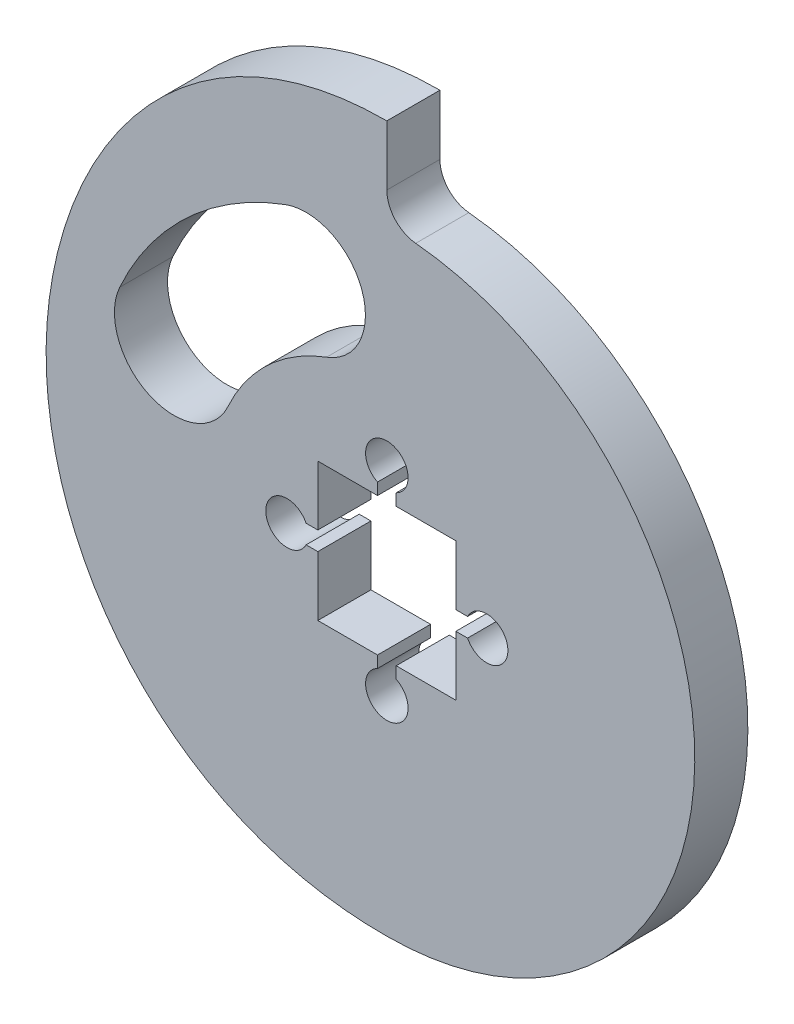
SolidWorks part; units mm, degrees
material "AISI 1020 Steel, Cold Rolled"
ref_plane "Front Plane" through (0, 0, 0) normal (0, 0, 1) x (1, 0, 0)
ref_plane "Top Plane" through (0, 0, 0) normal (0, 1, 0) x (1, 0, 0)
ref_plane "Right Plane" through (0, 0, 0) normal (1, 0, 0) x (0, 0, -1)
other "Center of Mass"
sketch "Sketch1" plane through (0, 0, 0) normal (0, 0, 1) x (1, 0, 0)
  line L0 (1.1176, -8.255) -> (8.255, -8.255)
  line L1 (-8.255, 8.255) -> (-1.1176, 8.255)
  line L2 (-8.255, 8.255) -> (-8.255, 1.1176)
  line L3 (-8.255, -8.255) -> (-1.1176, -8.255)
  line L4 (8.255, 8.255) -> (8.255, 1.1176)
  line L5 (8.255, -1.1176) -> (8.255, -8.255)
  line L6 (1.1176, 8.255) -> (8.255, 8.255)
  line L7 (8.255, 8.255) -> (-8.255, -8.255) construction
  line L9 (-9.6571, 1.1176) -> (-8.255, 1.1176)
  line L11 (-9.6571, -1.1176) -> (-8.255, -1.1176)
  line L14 (-1.1176, 9.6571) -> (-1.1176, 8.255)
  line L16 (1.1176, 9.6571) -> (1.1176, 8.255)
  line L25 (0, 0) -> (11.938, 0) construction
  line L27 (-8.255, -1.1176) -> (-8.255, -8.255)
  line L28 (0, 47.625) -> (0, 36.83)
  line L45 (-1.1176, -8.255) -> (-1.1176, -9.6571)
  line L47 (1.1176, -8.255) -> (1.1176, -9.6571)
  line L48 (8.255, -1.1176) -> (9.6571, -1.1176)
  line L50 (8.255, 1.1176) -> (9.6571, 1.1176)
  arc A2 (-1.1176, -9.6571) -> (1.1176, -9.6571) centre (0, -11.938) ccw
  arc A3 (9.6571, -1.1176) -> (9.6571, 1.1176) centre (11.938, 0) ccw
  arc A31 (-9.6571, 1.1176) -> (-9.6571, -1.1176) centre (-11.938, 0) ccw
  arc A32 (1.1176, 9.6571) -> (-1.1176, 9.6571) centre (0, 11.938) ccw
  arc A41 (0, -36.83) -> (0, 36.83) centre (0, 0) ccw
  spline S0 degree 3 poles (0, 47.625) (-26.6002, 47.625) (-56.1496, -0.4046) (-24.1552, -36.9841) (0, -36.83) knots 0 0 0 0 0.529165 1 1 1 1
  dimension "D2" = 11.938
  dimension "D4" = 5.08
  dimension "D6" = 16.51
  dimension "D7" = 40.64
  dimension "D14" = 73.66
  dimension "D3" = 47.625
  dimension "D1" = 16.51
  dimension "D5" = 2.2352
extrude "Boss-Extrude1" add sketch "Sketch1" along normal blind 6.35 contours A32 L16 L6 L4 L50 A3 L48 L5 L0 L47 A2 L45 L3 L27 L11 A31 L9 L2 L1 L14 region at (-1.1468, 42.2275, 0)
sketch "Sketch5" plane through (0, 0, 6.35) normal (0, 0, 1) x (1, 0, 0)
  arc A0 (-25.4675, 11.4914) -> (-9.6739, 26.2118) centre (0, 0) cw construction
  arc A1 (-12.1364, 32.8839) -> (-31.9501, 14.4164) centre (0, 0) ccw
  arc A2 (-7.2115, 19.5397) -> (-18.9848, 8.5663) centre (0, 0) ccw
  arc A3 (-7.2115, 19.5397) -> (-12.1364, 32.8839) centre (-9.6739, 26.2118) ccw
  arc A4 (-31.9501, 14.4164) -> (-18.9848, 8.5663) centre (-25.4675, 11.4914) ccw
  point P4 (-19.05, 20.4387)
  dimension "D1" = 27.94
  dimension "D2" = 7.112
  dimension "D3" = 21.59
  dimension "D4" = 19.05
extrude "Cut-Extrude1" cut sketch "Sketch5" against normal through all
fillet "Fillet2" radius 3.81 1 edges at (0, 36.83, 3.175)
